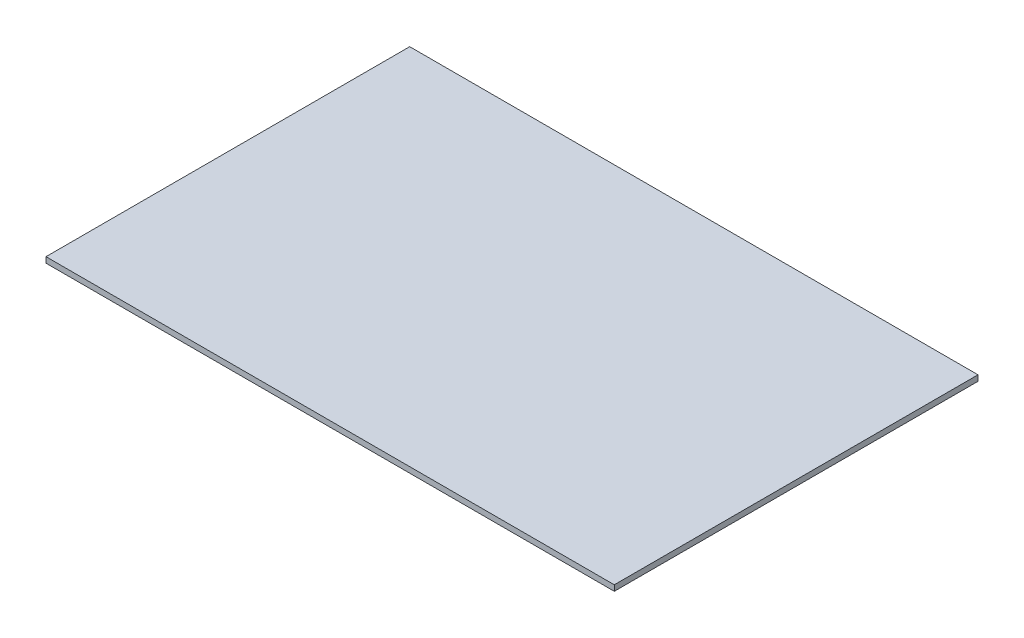
SolidWorks part; units mm, degrees
material "Pine"
ref_plane "Front Plane" through (0, 0, 0) normal (0, 0, 1) x (1, 0, 0)
ref_plane "Top Plane" through (0, 0, 0) normal (0, 1, 0) x (1, 0, 0)
ref_plane "Right Plane" through (0, 0, 0) normal (1, 0, 0) x (0, 0, -1)
sketch "Sketch1" plane through (0, 0, 0) normal (0, 1, 0) x (1, 0, 0)
  line L1 (-635, -406.4) -> (635, -406.4)
  line L2 (-635, -406.4) -> (-635, 406.4)
  line L3 (-635, 406.4) -> (635, 406.4)
  line L4 (635, -406.4) -> (635, 406.4)
  line L5 (-635, -406.4) -> (635, 406.4) construction
  line L6 (-635, 406.4) -> (635, -406.4) construction
  point P0 (0, 0)
  dimension "D1" = 812.8
  dimension "D2" = 1270
extrude "Boss-Extrude1" add sketch "Sketch1" along normal blind 12.7
